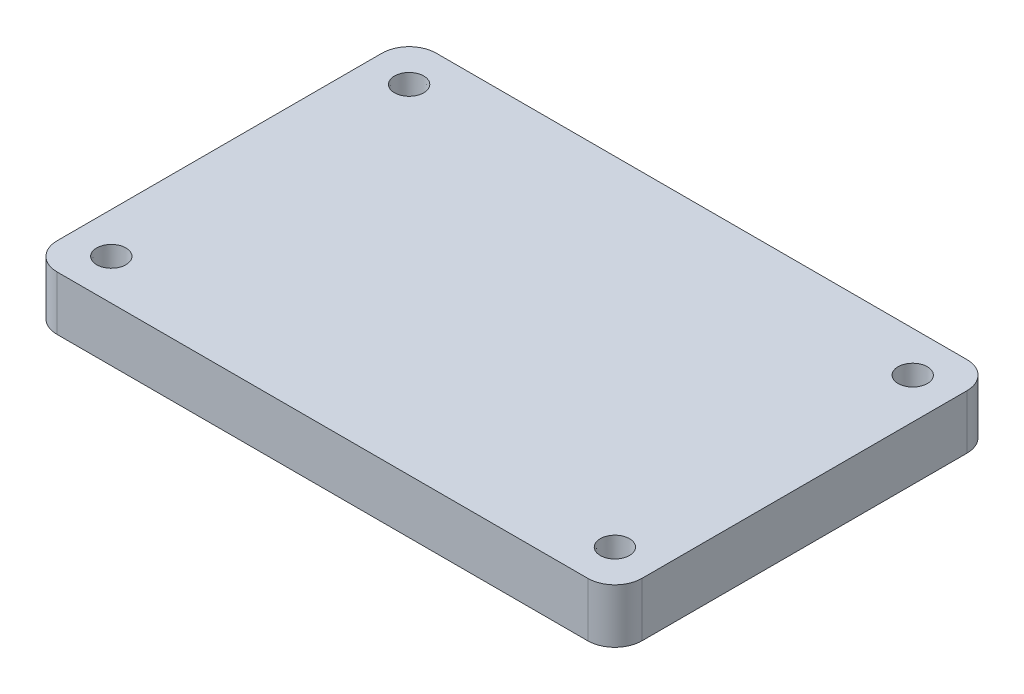
SolidWorks part; units mm, degrees
ref_plane "Front Plane" through (0, 0, 0) normal (0, 0, 1) x (1, 0, 0)
ref_plane "Top Plane" through (0, 0, 0) normal (0, 1, 0) x (1, 0, 0)
ref_plane "Right Plane" through (0, 0, 0) normal (1, 0, 0) x (0, 0, -1)
sketch "Sketch1" plane through (0, 0, 0) normal (0, 1, 0) x (1, 0, 0)
  line L1 (-54, -35) -> (54, -35)
  line L2 (-54, -35) -> (-54, 35)
  line L3 (-54, 35) -> (54, 35)
  line L4 (54, -35) -> (54, 35)
  line L5 (-54, -35) -> (54, 35) construction
  line L6 (-54, 35) -> (54, -35) construction
  point P0 (0, 0)
  dimension "D1" = 108
  dimension "D2" = 70
extrude "Boss-Extrude1" add sketch "Sketch1" along normal blind 10
sketch "Sketch2" plane through (0, 10, 0) normal (0, 1, 0) x (1, 0, 0)
  line L0 (46.5, 27.5) -> (-46.5, 27.5) construction
  line L1 (-49, -30) -> (49, -30) construction
  line L2 (-49, -30) -> (-49, 30) construction
  line L3 (-49, 30) -> (49, 30) construction
  line L4 (49, -30) -> (49, 30) construction
  line L5 (-49, -30) -> (49, 30) construction
  line L6 (-49, 30) -> (49, -30) construction
  line L7 (-46.5, 27.5) -> (-46.5, -27.5) construction
  line L8 (-46.5, -27.5) -> (46.5, -27.5) construction
  line L9 (46.5, -27.5) -> (46.5, 27.5) construction
  point P0 (0, 0)
  point P6 (-46.5, 27.5)
  point P7 (46.5, 27.5)
  point P8 (46.5, -27.5)
  point P9 (-46.5, -27.5)
  point P12 (0, 27.5)
  point P15 (-46.5, 0)
  dimension "D1" = 98
  dimension "D2" = 60
  dimension "D3" = 2.5
  dimension "D4" = 2.5
hole_wizard "Hole1" positions "Sketch3" profile "Sketch4" legacy
sketch "Sketch3" plane through (0, 10, 0) normal (0, 1, 0) x (1, 0, 0)
  point P0 (46.5, 27.5)
  point P3 (-46.5, 27.5)
  point P6 (-46.5, -27.5)
  point P9 (46.5, -27.5)
sketch "Sketch4" plane through (46.5, 10, -27.5) normal (1, 0, 0) x (0, 0, 1)
  line L0 (0, 0) -> (0, 8)
  line L1 (0, 8) -> (2.4, 8)
  line L2 (2.4, 8) -> (2.4, 6)
  line L3 (2.4, 6) -> (2.7, 6)
  line L4 (2.7, 6) -> (2.7, 0)
  line L5 (2.7, 0) -> (0, 0)
  line L6 (0, 110) -> (0, -10) construction
  dimension "Diameter" = 4.8
  dimension "Depth" = 8
  dimension "C-Bore Diameter" = 5.4
  dimension "C-Bore Depth" = 6
sketch "Sketch5" plane through (0, 0, 0) normal (0, -1, 0) x (1, 0, 0)
  line L0 (-20.3, 0) -> (20.3, 0) construction
  point P3 (0, 0)
  point P5 (-20.3, 0)
  point P6 (20.3, 0)
  dimension "D1" = 40.6
fillet "Fillet1" radius 5 4 edges at (-54, 5, 35) (-54, 5, -35) (54, 5, -35) (54, 5, 35)
hole_wizard "Hole3" positions "Sketch8" profile "Sketch9" legacy
sketch "Sketch8" plane through (0, 0, 0) normal (0, -1, 0) x (-1, 0, 0)
  line L0 (-30, 27.5) -> (30, 27.5) construction
  line L1 (30, 27.5) -> (30, -27.5) construction
  line L2 (30, -27.5) -> (-30, -27.5) construction
  line L3 (-30, -27.5) -> (-30, 27.5) construction
  line L6 (-46.5, 27.5) -> (46.5, 27.5) construction
  point P0 (-20.3, 0)
  point P3 (20.3, 0)
  point P7 (-30, 27.5)
  point P9 (30, 27.5)
  point P11 (30, -27.5)
  point P13 (-30, -27.5)
  point P28 (0, 0)
  point P29 (-30, 0)
  point P30 (0, 27.5)
  point P33 (0, 27.5)
  point P34 (0, 0)
  dimension "D1" = 60
sketch "Sketch9" plane through (20.3, 0, 0) normal (1, 0, 0) x (0, 0, -1)
  line L0 (0, 0) -> (0, 8)
  line L1 (0, 8) -> (2.4, 8)
  line L2 (2.4, 8) -> (2.4, 6)
  line L3 (2.4, 6) -> (2.7, 6)
  line L4 (2.7, 6) -> (2.7, 0)
  line L5 (2.7, 0) -> (0, 0)
  line L6 (0, 110) -> (0, -10) construction
  dimension "Diameter" = 4.8
  dimension "Depth" = 8
  dimension "C-Bore Diameter" = 5.4
  dimension "C-Bore Depth" = 6
chamfer "Chamfer1" distance 6 distance2 0.3 10 edges at (-46.5, 4, 30.2) (46.5, 4, 30.2) (46.5, 4, -24.8) (-46.5, 4, -24.8) (-30, 6, 24.8) (30, 6, 24.8) (20.3, 6, -2.7) (-20.3, 6, -2.7) (-30, 6, -30.2) (30, 6, -30.2) first distance on face at (-46.5, 4, 30.2) first distance on face at (46.5, 4, 30.2) first distance on face at (46.5, 4, -24.8) first distance on face at (-46.5, 4, -24.8) first distance on face at (-30, 6, 24.8) first distance on face at (30, 6, 24.8) first distance on face at (20.3, 6, -2.7) first distance on face at (-20.3, 6, -2.7) first distance on face at (-30, 6, -30.2) first distance on face at (30, 6, -30.2)
